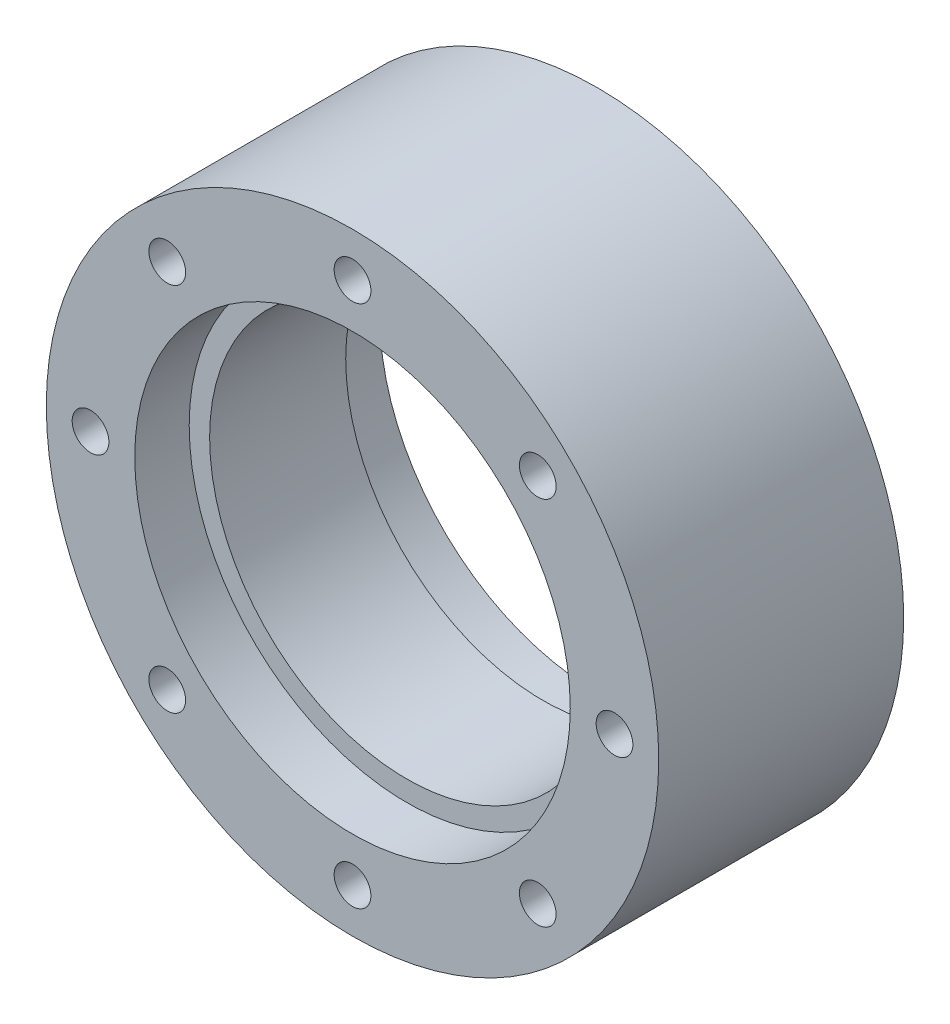
SolidWorks part; units mm, degrees
ref_plane "Front Plane" through (0, 0, 0) normal (0, 0, 1) x (1, 0, 0)
ref_plane "Top Plane" through (0, 0, 0) normal (0, 1, 0) x (1, 0, 0)
ref_plane "Right Plane" through (0, 0, 0) normal (1, 0, 0) x (0, 0, -1)
ref_axis "Z" through (0, 0, 9.9) along (0, 0, -1)
sketch "Sketch7" plane through (0, 0, 0) normal (0, 1, 0) x (1, 0, 0)
  line L0 (16, 9) -> (16, 5)
  line L2 (16, 5) -> (14.5, 5)
  line L5 (16, 9) -> (22.5, 9)
  line L6 (22.5, 9) -> (22.5, -9)
  line L7 (24.7452, 0) -> (-6.4078, 0) construction
  line L8 (16, -5) -> (14.5, -5)
  line L9 (16, -9) -> (16, -5)
  line L10 (14.5, 5) -> (14.5, -5)
  line L11 (22.5, -9) -> (16, -9)
  line L12 (0, -9.9) -> (0, 9.9) construction
  point P6 (0, 0)
  point P15 (19, 8.1756)
  point P16 (0, 0)
  dimension "D2" = 4
  dimension "D4" = 5
  dimension "D1" = 14.5
  dimension "D3" = 16
  dimension "D5" = 22.5
revolve "Revolve1" add sketch "Sketch7" angle 360 about axis through (0, 0, 9.9) along (0, 0, -1)
sketch "Sketch3" plane through (0, 0, 0) normal (0, 0, 1) x (1, 0, 0)
  line L0 (0, 0) -> (0, 19.25) construction
  circle A0 centre (0, 19.25) radius 1.35
  point P2 (-2.3677, 22.7393)
  point P4 (0, 0)
  dimension "D1" = 2.7
  dimension "D2" = 19.25
extrude "Cut-Extrude2" cut sketch "Sketch3" against normal through all both and the other way through all
sketch "Sketch4" plane through (0, 0, -9) normal (0, 0, -1) x (-1, 0, 0)
  circle A0 centre (0, 19.25) radius 2.25
  circle A1 centre (0, 19.25) radius 1.35 construction
  dimension "D1" = 4.5
extrude "Cut-Extrude4" cut sketch "Sketch4" against normal blind 2.5 and the other way through all
chamfer "Chamfer1" distance 0.1 angle 45 1 edges at (-1.35, 19.25, -6.5)
pattern_circular "CirPattern3" count 4 over 360 about axis through (0, 0, 9.9) along (0, 0, -1) of "Cut-Extrude4"
pattern_circular "CirPattern2" count 8 over 360 about axis through (0, 0, 9.9) along (0, 0, -1) of "Cut-Extrude2"
equation "\"BearingBaseDistance\"= 10"
equation "\"BearingOD\"= 32"
equation "\"BearingHeight\"= 4"
equation "\"SeatsOD\"= \"BearingOD\" + 10"
equation "\"WireHarnessHeight\"= 4"
equation "\"OuterWallWidth\"= 6"
equation "\"OverallOD\" = 45"
equation "\"BearingID\" = 25"
equation "\"OverallHeight\"= \"WireHarnessHeight\" + \"BearingHeight\"*2 + \"BearingBaseDistance\""
equation "\"RetainingRingThickness\" = 1.30"
equation "\"RetaininRingGrooveDiameter\" = 23.9"
equation "\"ShaftLengthAfterFlange\" = 2*\"BearingHeight\" + \"BearingBaseDistance\" + \"RetainingRingThickness\"*2\t'give a retaining ring thickness of extra clearance"
equation "\"RetainingRingGrooveBase\" = \"ShaftLengthAfterFlange\" - \"RetainingRingThickness\"*2"
equation "\"CoverThickness\" = 1"
equation "\"CoverClearance\" = 1"
equation "\"FlangHeight\" = \"CoverThickness\" + \"CoverClearance\" + \"WireHarnessHeight\""
equation "\"OuterHousingHeight\" = \"WireHarnessHeight\" + \"BearingHeight\"*2 + \"BearingBaseDistance\""
equation "\"PCBWidth\" = 5"
equation "\"PCBHeight\" = \"OuterHousingHeight\" "
equation "\"PCBThickness\" = 1"
equation "\"NormalDistSidewallPCBToZ\" = (\"OverallOD\"/2) - 1.6\t'radial distance from the z axis to pcb origin on the top/connector side"
equation "\"PCBSidewallCutoutClearance\" = 0.1"
equation "\"D3@Sketch7\"=\"BearingOD\"/2"
equation "\"D4@Sketch7\"=\"BearingBaseDistance\"/2"
equation "\"D5@Sketch7\"=\"OverallOD\"/2"
equation "\"D2@Sketch3\"=(\"OverallOD\"+\"BearingOD\")/4"
